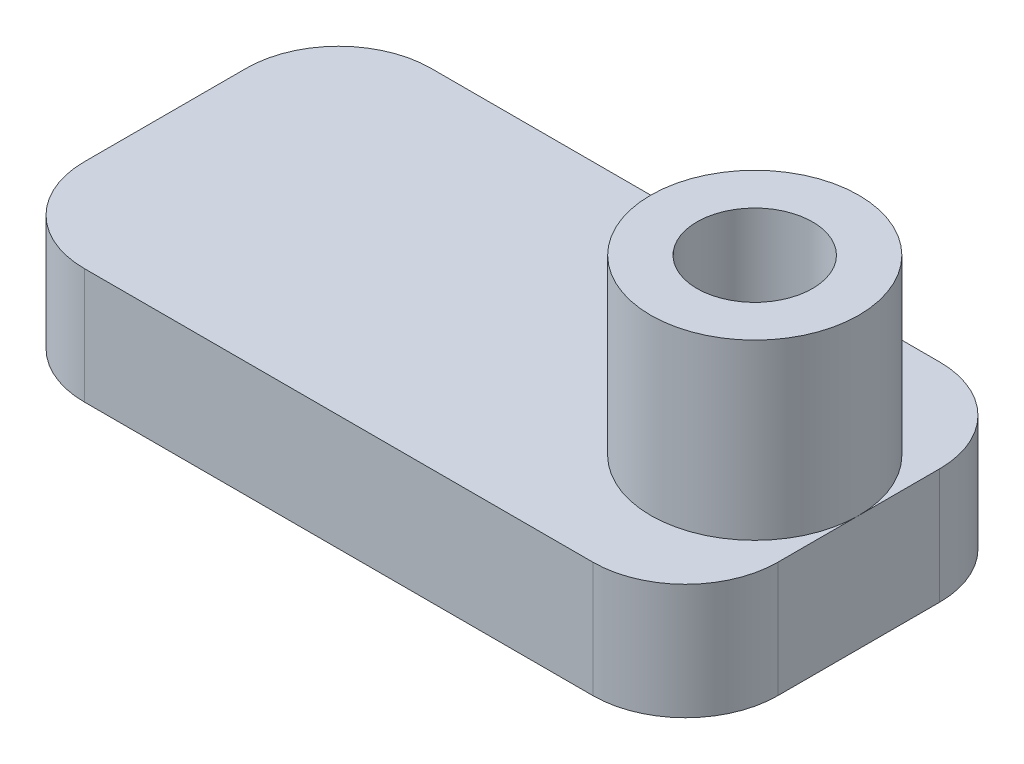
SolidWorks part; units mm, degrees
ref_plane "Front Plane" through (0, 0, 0) normal (0, 0, 1) x (1, 0, 0)
ref_plane "Top Plane" through (0, 0, 0) normal (0, 1, 0) x (1, 0, 0)
ref_plane "Right Plane" through (0, 0, 0) normal (1, 0, 0) x (0, 0, -1)
sketch "Sketch1" plane through (0, 0, 0) normal (0, 1, 0) x (1, 0, 0)
  line L1 (-51, 15) -> (9, 15)
  line L2 (-51, 15) -> (-51, -15)
  line L3 (-51, -15) -> (9, -15)
  line L4 (9, 15) -> (9, -15)
  circle A0 centre (0, 0) radius 5
  circle A1 centre (0, 0) radius 9
  point P8 (9, 0)
  dimension "D1" = 10
  dimension "D2" = 18
  dimension "D3" = 30
  dimension "D4" = 60
extrude "Boss-Extrude1" add sketch "Sketch1" along normal blind 10 contours L4 A1 L1 L2 L3 | A1 A0 region at (-8.7454, 0, 0) region at (-24.4576, 0, 0)
fillet "Fillet1" radius 8 4 edges at (-51, 5, 15) (-51, 5, -15) (9, 5, -15) (9, 5, 15)
extrude "Boss-Extrude2" add sketch "Sketch1<3>" along normal blind 25 contours A1 A0 region at (-8.7454, 0, 0)
sketch "Sketch1<3>" plane through (0, 0, 0) normal (0, 1, 0) x (1, 0, 0) same geometry as "Sketch1"
equation "\"D2@Sketch1\"=10.00mm+8"
